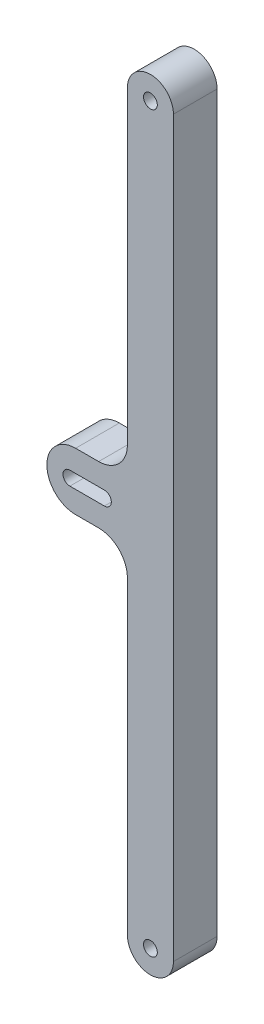
SolidWorks part; units mm, degrees
note: The reader was unsure of these and kept them because the rebuilt part matched: shared geometry of "草图1<4>".
ref_plane "前视基准面" through (0, 0, 0) normal (0, 0, 1) x (1, 0, 0)
ref_plane "上视基准面" through (0, 0, 0) normal (0, 1, 0) x (1, 0, 0)
ref_plane "右视基准面" through (0, 0, 0) normal (1, 0, 0) x (0, 0, -1)
other "Configuration Table"
sketch "草图1" plane through (0, 0, 0) normal (0, 0, 1) x (1, 0, 0)
  circle A0 centre (0, 0) radius 2
  circle A1 centre (0, 0) radius 0.6
  dimension "D1" = 4
  dimension "D2" = 1.2
extrude "凸台-拉伸1" add sketch "草图1" along normal blind 3.8
sketch "草图2" plane through (0, 0, 0) normal (0, 1, 0) x (1, 0, 0)
  line L0 (2, 0) -> (-2, 0) construction
  line L1 (-2, 0) -> (2, 0)
  line L2 (-2, 0) -> (-2, -3.8)
  line L3 (-2, -3.8) -> (2, -3.8)
  line L4 (2, 0) -> (2, -3.8)
  line L5 (-2, 0) -> (-2, -3.8) construction
  line L6 (-2, -3.8) -> (2, -3.8) construction
  line L7 (2, -3.8) -> (2, 0) construction
extrude "凸台-拉伸2" add sketch "草图2" against normal blind 10
extrude "切除-拉伸1" cut sketch "草图1<4>" along normal through all contours A1
sketch "草图1<4>" plane through (0, 0, 0) normal (0, 0, 1) x (1, 0, 0) same geometry as "草图1"
sketch "草图3" plane through (0, 0, 3.8) normal (0, 0, 1) x (1, 0, 0)
  line L1 (-2, -10) -> (-2, 0) construction
  line L2 (2, -10) -> (-2, -10)
  line L3 (2, -10) -> (2, -31.9)
  line L4 (2, -31.9) -> (-2, -31.9)
  line L5 (-2, -10) -> (-2, -31.9)
  line L6 (2, -10) -> (2, 0) construction
  line L7 (-2, -10) -> (2, -10) construction
  dimension "D1" = 31.9
extrude "凸台-拉伸3" add sketch "草图3" against normal up to surface (3.8 mm away) up to face at (0, -4.5, 0)
mirror "镜向1" about plane through (2, -31.9, -22.2623) normal (0, -1, 0) of bodies 227
sketch "草图5" plane through (0, 0, 3.8) normal (0, 0, 1) x (1, 0, 0)
  line L0 (-2, -63.8) -> (-2, 0) construction
  line L1 (-2, -29.4) -> (-9, -29.4)
  line L2 (-2, -29.4) -> (-2, -34.4)
  line L3 (-2, -34.4) -> (-9, -34.4)
  line L4 (-9, -29.4) -> (-9, -34.4)
  line L5 (-9, -31.9) -> (-2, -31.9) construction
  point P8 (-8.9148, -27.6018)
  point P9 (-6.2408, -27.6018)
  point P10 (0, 0)
  dimension "D1" = 7
  dimension "D2" = 5
extrude "凸台-拉伸4" add sketch "草图5" against normal up to surface (3.8 mm away) up to face at (0, -31.9, 0)
sketch "草图6" plane through (0, 0, 3.8) normal (0, 0, 1) x (1, 0, 0)
  line L0 (-4, -31.9) -> (-7, -31.9) construction
  line L1 (-4, -32.5) -> (-7, -32.5)
  line L2 (-4, -31.3) -> (-7, -31.3)
  line L3 (-7, -31.9) -> (-9, -31.9) construction
  line L4 (-9, -29.4) -> (-9, -34.4) construction
  line L5 (-2, -63.8) -> (-2, -34.4) construction
  arc A0 (-4, -32.5) -> (-4, -31.3) centre (-4, -31.9) ccw
  arc A1 (-7, -31.3) -> (-7, -32.5) centre (-7, -31.9) ccw
  point P2 (-5.5, -31.9)
  dimension "D1" = 2
  dimension "D2" = 1.2
  dimension "D3" = 2
extrude "切除-拉伸3" cut sketch "草图6" against normal through all
fillet "圆角1" radius 2.5 6 edges at (-2, -29.4, 1.9) (-2, -34.4, 1.9) (-9, -34.4, 1.9) (-9, -29.4, 1.9) (-9, -31.9, 3.8) (-9, -31.9, 0)
